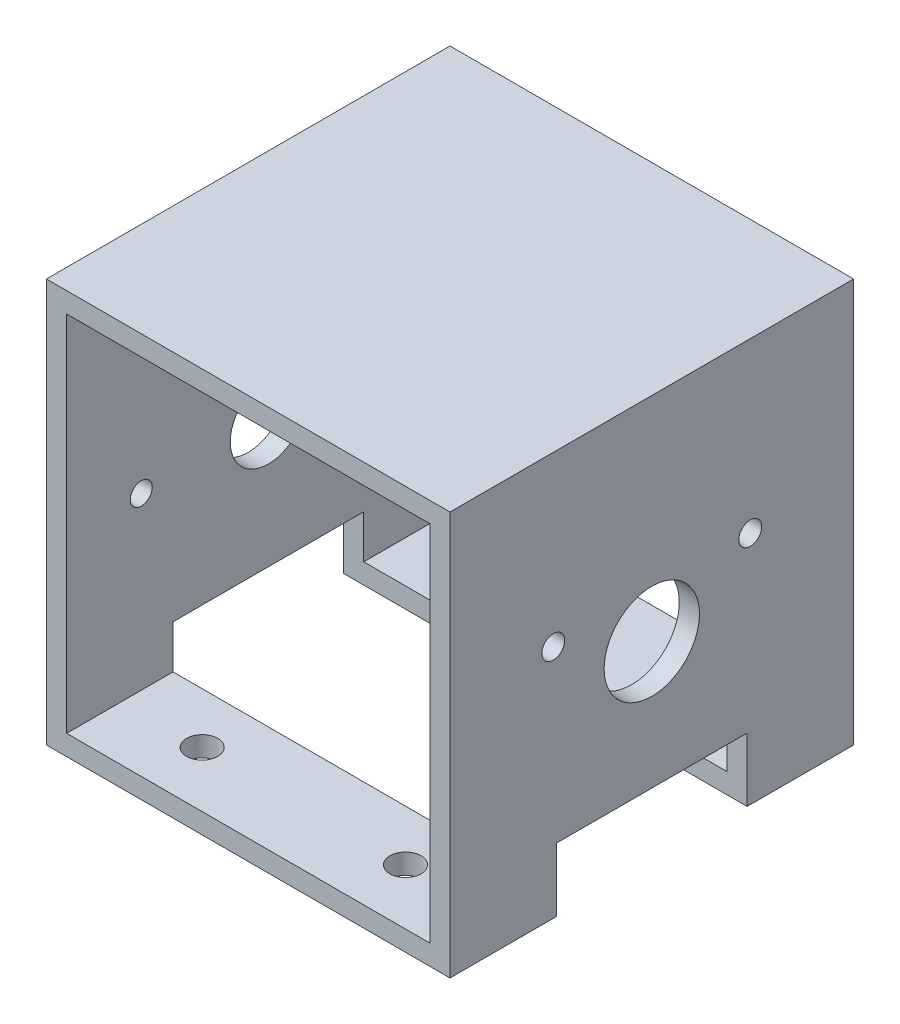
SolidWorks part; units mm, degrees
ref_plane "Front Plane" through (0, 0, 0) normal (0, 0, 1) x (1, 0, 0)
ref_plane "Top Plane" through (0, 0, 0) normal (0, 1, 0) x (1, 0, 0)
ref_plane "Right Plane" through (0, 0, 0) normal (1, 0, 0) x (0, 0, -1)
sketch "Sketch1" plane through (0, 0, 0) normal (0, 0, 1) x (1, 0, 0)
  line L1 (-31.75, -31.75) -> (31.75, -31.75)
  line L2 (-31.75, -31.75) -> (-31.75, 31.75)
  line L3 (-31.75, 31.75) -> (31.75, 31.75)
  line L4 (31.75, -31.75) -> (31.75, 31.75)
  line L5 (-31.75, -31.75) -> (31.75, 31.75) construction
  line L6 (-31.75, 31.75) -> (31.75, -31.75) construction
  point P0 (0, 0)
  dimension "D1" = 63.5
extrude "Extrude-Thin1" add sketch "Sketch1" along normal blind 63.5 thin thin type one direction reverse wall 3.175
sketch "Sketch2" plane through (31.75, 0, 0) normal (1, 0, 0) x (0, 0, -1)
  line L0 (-63.5, -31.75) -> (0, -31.75) construction
  line L1 (-16.75, -41.75) -> (-46.75, -41.75)
  line L2 (-16.75, -41.75) -> (-16.75, -21.75)
  line L3 (-16.75, -21.75) -> (-46.75, -21.75)
  line L4 (-46.75, -41.75) -> (-46.75, -21.75)
  line L5 (-16.75, -41.75) -> (-46.75, -21.75) construction
  line L6 (-16.75, -21.75) -> (-46.75, -41.75) construction
  point P0 (-31.75, -31.75)
  dimension "D1" = 30
  dimension "D2" = 10
extrude "Cut-Extrude1" cut sketch "Sketch2" against normal through all contours L1 L4 L3 L2
sketch "Sketch5" plane through (28.575, 11.8301, 29.9884) normal (-1, 0, 0) x (0, 0, 1)
  line L0 (1.7616, -13.5801) -> (1.7616, -33.5801) construction
  line L1 (16.7616, -33.5801) -> (-13.2384, -33.5801) construction
  circle A0 centre (1.7616, -13.5801) radius 7.5
  dimension "D1" = 15
  dimension "D2" = 20
extrude "Cut-Extrude3" cut sketch "Sketch5" against normal through all
hole_wizard "M3 Clearance Hole1" positions "Sketch7" profile "Sketch9" hole size "M3" standard "ANSI Metric" end condition through all
sketch "Sketch7" plane through (28.575, 11.8301, 29.9884) normal (-1, 0, 0) x (0, 0, 1)
  line L0 (-13.7384, -6.5801) -> (17.2616, -6.5801)
  line L2 (-6.1211, -20.0801) -> (-6.1211, 6.9199)
  line L4 (-6.1211, 6.9199) -> (17.2616, -6.5801)
  line L8 (1.7616, -13.5801) -> (1.7616, -6.5801) construction
  line L11 (1.7616, -6.5801) -> (-6.1211, -6.5801)
  circle A0 centre (1.7616, -6.5801) radius 18.5
  circle A2 centre (1.7616, -13.5801) radius 7.5 construction
  point P0 (-13.7384, -6.5801)
  point P2 (17.2616, -6.5801)
  dimension "D4" = 37
  dimension "D1" = 31
  dimension "D2" = 27
  dimension "D3" = 7
sketch "Sketch9" plane through (28.575, 5.25, 16.25) normal (0, 1, 0) x (0, 0, 1)
  line L0 (0, 0) -> (0, 3.175)
  line L1 (0, 3.175) -> (1.8, 3.175)
  line L2 (1.8, 3.175) -> (1.8, 0)
  line L5 (1.8, 0) -> (0, 0)
  line L11 (0, -6.35) -> (0, 107.95) construction
  dimension "Thru Hole Dia." = 3.6
  dimension "Thru Hole Depth" = 3.175
hole_wizard "#8-32 Tapped Hole1" positions "Sketch12" profile "Sketch11" tap size "#8-32" standard "ANSI Inch" end condition up to next
sketch "Sketch12" plane through (-31.75, 0, 0) normal (-1, 0, 0) x (0, 0, 1)
  line L0 (11.75, -1.75) -> (51.75, -1.75)
  circle A0 centre (31.75, -1.75) radius 7.5 construction
  circle A1 centre (31.75, -1.75) radius 7.5
  point P0 (51.75, -1.75)
  point P2 (11.75, -1.75)
  dimension "D1" = 40
sketch "Sketch11" plane through (-31.75, -1.75, 51.75) normal (0, 1, 0) x (0, 0, 1)
  line L0 (0, 0) -> (0, 3.175)
  line L1 (0, 3.175) -> (1.7272, 3.175)
  line L2 (1.7272, 3.175) -> (1.7272, 0)
  line L5 (1.7272, 0) -> (0, 0)
  line L11 (0, -6.35) -> (0, 107.95) construction
  dimension "Thru Tap Drill Dia." = 3.4544
  dimension "Thru Tap Drill Depth" = 3.175
cosmetic thread "Hole Thread1" parameters "D2"=4.1656
cosmetic thread "Hole Thread2" parameters "D2"=4.1656
sketch "Sketch13" plane through (-31.75, 0, 0) normal (-1, 0, 0) x (0, 0, 1)
  circle A0 centre (31.75, -1.75) radius 7.5 construction
  circle A1 centre (31.75, -1.75) radius 7.5 construction
  circle A2 centre (31.75, -1.75) radius 6
  dimension "D1" = 12
extrude "Cut-Extrude4" cut sketch "Sketch13" against normal up to next
hole_wizard "#8 Clearance Hole1" positions "Sketch15" profile "Sketch14" hole size "#8" standard "ANSI Inch" end condition up to next
sketch "Sketch15" plane through (0, -31.75, 0) normal (0, -1, 0) x (-1, 0, 0)
  line L0 (-16, -8.75) -> (16, -8.75)
  line L1 (16, -8.75) -> (16, -54.75)
  line L2 (16, -54.75) -> (-16, -54.75)
  line L3 (-16, -54.75) -> (-16, -8.75)
  line L23 (0, -8.75) -> (0, 0)
  line L24 (31.75, 0) -> (-31.75, 0) construction
  line L29 (31.75, -46.75) -> (31.75, -16.75)
  line L31 (16, -31.75) -> (31.75, -31.75)
  point P0 (16, -8.75)
  point P2 (-16, -8.75)
  point P4 (-16, -54.75)
  point P6 (16, -54.75)
  dimension "D1" = 32
  dimension "D2" = 46
sketch "Sketch14" plane through (-16, -31.75, 8.75) normal (1, 0, 0) x (0, 0, -1)
  line L0 (0, 0) -> (0, 3.175)
  line L1 (0, 3.175) -> (2.4574, 3.175)
  line L2 (2.4574, 3.175) -> (2.4574, 0)
  line L5 (2.4574, 0) -> (0, 0)
  line L11 (0, -6.35) -> (0, 107.95) construction
  dimension "Thru Hole Dia." = 4.9149
  dimension "Thru Hole Depth" = 3.175
